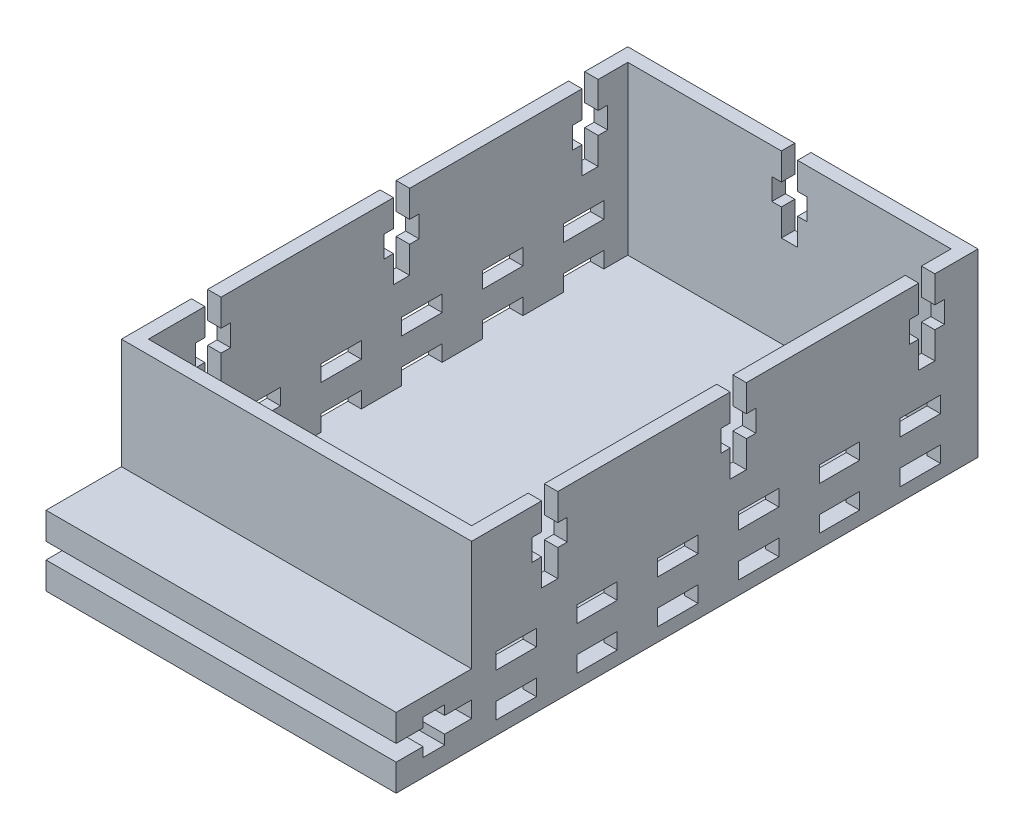
SolidWorks part; units mm, degrees
ref_plane "Front Plane" through (0, 0, 0) normal (0, 0, 1) x (1, 0, 0)
ref_plane "Top Plane" through (0, 0, 0) normal (0, 1, 0) x (1, 0, 0)
ref_plane "Right Plane" through (0, 0, 0) normal (1, 0, 0) x (0, 0, -1)
sketch "Sketch1" plane through (0, 0, 0) normal (0, 1, 0) x (1, 0, 0)
  line L1 (-30, 44.5) -> (30, 44.5)
  line L2 (-30, 44.5) -> (-30, -44.5)
  line L3 (-30, -44.5) -> (30, -44.5)
  line L4 (30, 44.5) -> (30, -44.5)
  point P4 (0, 44.5)
  point P6 (-30, 0)
  dimension "D1" = 89
  dimension "D2" = 60
extrude "Boss-Extrude1" add sketch "Sketch1" along normal blind 2.5
sketch "Sketch3" plane through (0, 0, 0) normal (0, 1, 0) x (1, 0, 0)
  line L0 (-30, 44.5) -> (-30, -44.5) construction
  line L1 (-32.5, 47) -> (32.5, 47)
  line L2 (-32.5, 47) -> (-32.5, -47)
  line L3 (-32.5, -47) -> (32.5, -47)
  line L4 (32.5, 47) -> (32.5, -47)
  line L5 (30, 44.5) -> (-30, 44.5) construction
  line L6 (30, -44.5) -> (30, 44.5) construction
  line L7 (-30, -44.5) -> (30, -44.5) construction
  line L9 (-30, 44.5) -> (30, 44.5)
  line L10 (-30, 44.5) -> (-30, -44.5)
  line L11 (-30, -44.5) -> (30, -44.5)
  line L12 (30, 44.5) -> (30, -44.5)
  dimension "D1" = 2.5
  dimension "D2" = 2.5
  dimension "D3" = 2.5
  dimension "D4" = 2.5
extrude "Boss-Extrude2" add sketch "Sketch3" along normal blind 33.5
sketch "Sketch5" plane through (0, 0, 0) normal (1, 0, 0) x (0, 0, -1)
  line L0 (-47, 0) -> (47, 0) construction
  line L1 (-42.4651, 2.5) -> (-34.9651, 2.5)
  line L2 (-42.4651, 2.5) -> (-42.4651, 5.5)
  line L3 (-42.4651, 5.5) -> (-34.9651, 5.5)
  line L4 (-34.9651, 2.5) -> (-34.9651, 5.5)
  dimension "D1" = 2.5
  dimension "D2" = 3
  dimension "D3" = 7.5
extrude "Cut-Extrude1" cut sketch "Sketch5" against normal through all both and the other way through all
pattern_linear "LPattern1" count 6 spacing 15 along (0, 0, -1) of "Cut-Extrude1"
pattern_linear "LPattern2" count 2 spacing 8 along (0, 1, 0) of "LPattern1"
sketch "Sketch6" plane through (0, 0, 0) normal (0, 1, 0) x (1, 0, 0)
  line L0 (32.5, -47) -> (32.5, 47) construction
  line L1 (-32.5, -47) -> (32.5, -47)
  line L2 (-32.5, -47) -> (-32.5, -61)
  line L3 (-32.5, -61) -> (32.5, -61)
  line L4 (32.5, -47) -> (32.5, -61)
  dimension "D1" = 14
extrude "Boss-Extrude3" add sketch "Sketch6" along normal blind 13
sketch "Sketch7" plane through (0, 0, 0) normal (1, 0, 0) x (0, 0, -1)
  line L0 (-61, 8) -> (-56, 8)
  line L1 (-61, 13) -> (-61, 0) construction
  line L2 (-56, 8) -> (-56, 9.75)
  line L3 (-56, 9.75) -> (-52, 9.75)
  line L4 (-52, 9.75) -> (-52, 8)
  line L5 (-52, 8) -> (-47, 8)
  line L6 (-47, 8) -> (-47, 5)
  line L7 (-47, 5) -> (-52, 5)
  line L8 (-52, 5) -> (-52, 3.25)
  line L9 (-52, 3.25) -> (-56, 3.25)
  line L10 (-56, 3.25) -> (-56, 5)
  line L11 (-56, 5) -> (-61, 5)
  line L13 (-61, 8) -> (-61, 5)
  point P14 (-61, 6.5)
  point P15 (-61, 6.5)
  dimension "D1" = 5
  dimension "D2" = 4
  dimension "D3" = 3
  dimension "D4" = 1.75
  dimension "D5" = 1.75
  dimension "D6" = 5
extrude "Cut-Extrude2" cut sketch "Sketch7" against normal through all both and the other way through all
sketch "Sketch11" plane through (0, 0, 0) normal (1, 0, 0) x (0, 0, -1)
  line L12 (39, 33.5) -> (39, 28.5)
  line L13 (-47, 33.5) -> (47, 33.5) construction
  line L14 (39, 28.5) -> (40.75, 28.5)
  line L15 (40.75, 28.5) -> (40.75, 24.5)
  line L16 (40.75, 24.5) -> (39, 24.5)
  line L17 (39, 24.5) -> (39, 19.5)
  line L18 (39, 19.5) -> (36, 19.5)
  line L19 (36, 19.5) -> (36, 24.5)
  line L20 (36, 24.5) -> (34.25, 24.5)
  line L21 (34.25, 24.5) -> (34.25, 28.5)
  line L22 (34.25, 28.5) -> (36, 28.5)
  line L23 (36, 28.5) -> (36, 33.5)
  line L24 (36, 33.5) -> (39, 33.5)
  line L25 (47, 33.5) -> (47, 0) construction
  point P0 (37.5, 33.5)
  dimension "D7" = 5
  dimension "D8" = 4
  dimension "D9" = 1.75
  dimension "D10" = 1.75
  dimension "D11" = 5
  dimension "D12" = 3
  dimension "D2" = 9.5
extrude "Cut-Extrude3" cut sketch "Sketch11" against normal through all both and the other way through all
pattern_linear "LPattern3" count 3 spacing 35 along (0, 0, 1) of "Cut-Extrude3"
sketch "Sketch12" plane through (0, 0, 0) normal (0, 0, 1) x (1, 0, 0)
  line L0 (1.5, 33.5) -> (1.5, 28.5)
  line L1 (1.5, 28.5) -> (3.25, 28.5)
  line L2 (3.25, 28.5) -> (3.25, 24.5)
  line L3 (3.25, 24.5) -> (1.5, 24.5)
  line L4 (1.5, 24.5) -> (1.5, 19.5)
  line L5 (1.5, 19.5) -> (-1.5, 19.5)
  line L6 (-1.5, 19.5) -> (-1.5, 24.5)
  line L7 (-1.5, 24.5) -> (-3.25, 24.5)
  line L8 (-3.25, 24.5) -> (-3.25, 28.5)
  line L9 (-3.25, 28.5) -> (-1.5, 28.5)
  line L10 (-1.5, 28.5) -> (-1.5, 33.5)
  line L11 (-1.5, 33.5) -> (1.5, 33.5)
  line L12 (-32.5, 33.5) -> (32.5, 33.5) construction
  point P0 (0, 33.5)
  point P15 (0, 33.5)
  dimension "D1" = 5
  dimension "D2" = 4
  dimension "D3" = 1.75
  dimension "D4" = 1.75
  dimension "D5" = 5
  dimension "D6" = 3
extrude "Cut-Extrude4" cut sketch "Sketch12" against normal up to next
equation "\"wall\"=2.5"
equation "\"D1@Sketch3\"=\"wall\""
equation "\"D2@Sketch3\"=\"wall\""
equation "\"D3@Sketch3\"=\"wall\""
equation "\"D4@Sketch3\"=\"wall\""
equation "\"D1@Boss-Extrude2\"=\"wall\"+31"
equation "\"D1@Sketch5\"=\"wall\""
equation "\"prescrew\"=5"
equation "\"D1@Sketch7\"=\"prescrew\""
equation "\"nut\"=4"
equation "\"D2@Sketch7\"=\"nut\""
equation "\"nutextra\"=1.75"
equation "\"D5@Sketch7\"=\"nutextra\""
equation "\"D4@Sketch7\"=\"nutextra\""
equation "\"postscrew\"=5"
equation "\"D6@Sketch7\"=\"postscrew\""
equation "\"screw\"=3"
equation "\"D3@Sketch7\"=\"screw\""
equation "\"D7@Sketch11\"=\"prescrew\""
equation "\"D8@Sketch11\"=\"nut\""
equation "\"D9@Sketch11\"=\"nutextra\""
equation "\"D10@Sketch11\"=\"nutextra\""
equation "\"D11@Sketch11\"=\"postscrew\""
equation "\"D12@Sketch11\"=\"screw\""
equation "\"D2@Sketch11\"=\"wall\"+7"
